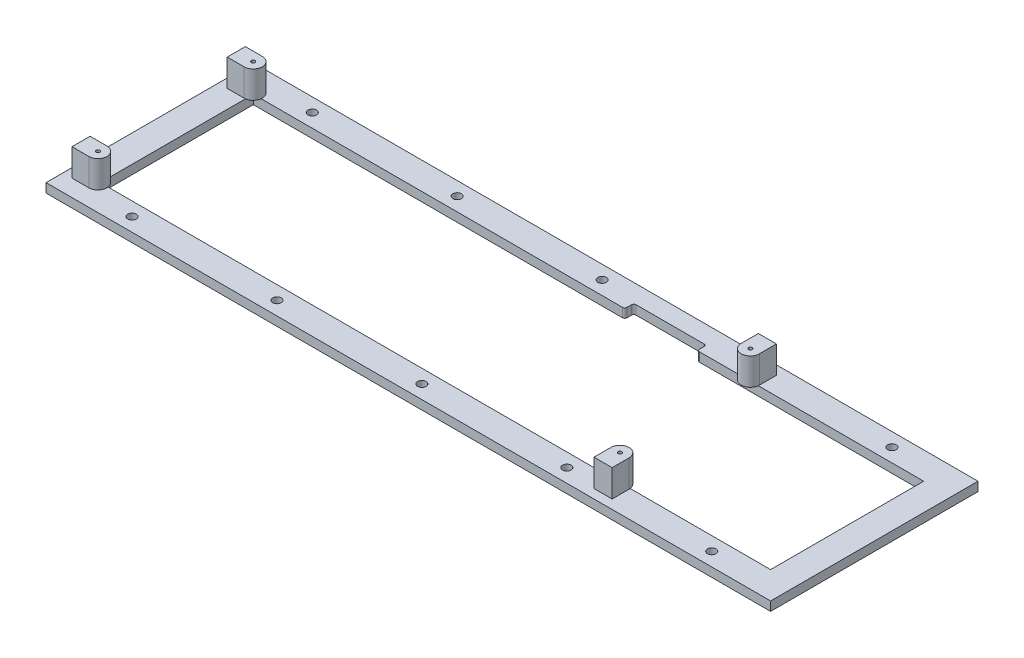
SolidWorks part; units mm, degrees
ref_plane "Front Plane" through (0, 0, 0) normal (0, 0, 1) x (1, 0, 0)
ref_plane "Top Plane" through (0, 0, 0) normal (0, 1, 0) x (1, 0, 0)
ref_plane "Right Plane" through (0, 0, 0) normal (1, 0, 0) x (0, 0, -1)
sketch "Sketch1" plane through (0, 0, 0) normal (0, 1, 0) x (1, 0, 0)
  line L0 (3.175, 3.175) -> (3.175, 69.5249) construction
  line L1 (0, 0) -> (254, 0)
  line L2 (0, 0) -> (0, 72.6999)
  line L3 (0, 72.6999) -> (254, 72.6999)
  line L4 (254, 0) -> (254, 72.6999)
  line L5 (6.35, 66.3499) -> (194.85, 66.3499) construction
  line L6 (6.35, 66.3499) -> (6.35, 6.35) construction
  line L7 (6.35, 6.35) -> (194.85, 6.35) construction
  line L8 (194.85, 66.3499) -> (194.85, 6.35) construction
  line L9 (3.175, 69.5249) -> (250.825, 69.5249) construction
  line L10 (250.825, 3.175) -> (250.825, 69.5249) construction
  line L11 (3.175, 3.175) -> (250.825, 3.175) construction
  line L12 (562.1369, 340.2788) -> (1927.4703, 340.2788) construction
  line L13 (3.175, 3.175) -> (3.175, 69.5249) construction
  line L28 (127, 72.6999) -> (127, 0) construction
  line L29 (127, 69.5249) -> (127, 66.3499) construction
  line L30 (0, 36.3499) -> (254, 36.3499) construction
  line L32 (6.35, 66.284) -> (6.35, 6.35) construction
  line L33 (6.35, 6.35) -> (194.851, 6.35) construction
  line L34 (194.851, 66.284) -> (194.851, 6.35) construction
  line L52 (-1511.8018, 332.3966) -> (-146.4685, 332.3966) construction
  line L54 (244.475, 63.1749) -> (244.475, 9.525)
  line L55 (244.475, 9.525) -> (9.525, 9.525)
  line L56 (9.525, 63.1749) -> (9.525, 9.525)
  line L57 (244.475, 63.1749) -> (9.525, 9.525) construction
  line L58 (244.475, 9.525) -> (9.525, 63.1749) construction
  line L62 (140.4938, 66.3499) -> (164.3062, 66.3499)
  line L63 (165.1, 63.9686) -> (165.1, 65.5561)
  line L64 (165.8938, 63.1749) -> (244.475, 63.1749)
  line L65 (127, 67.9374) -> (177.8, 67.9374) construction
  line L66 (139.7, 65.5561) -> (139.7, 63.9686)
  line L67 (138.9062, 63.1749) -> (9.525, 63.1749)
  line L68 (180.1749, 69.5249) -> (186.5249, 69.5249)
  line L69 (180.1749, 69.5249) -> (180.1749, 63.5332)
  line L70 (180.1749, 63.5332) -> (186.5249, 63.5332) construction
  line L71 (186.5249, 69.5249) -> (186.5249, 63.5332)
  line L72 (188.9252, 9.1008) -> (195.2752, 9.1008) construction
  line L73 (188.9252, 9.1008) -> (188.9252, 3.175)
  line L74 (188.9252, 3.175) -> (195.2752, 3.175)
  line L75 (195.2752, 9.1008) -> (195.2752, 3.175)
  line L76 (3.175, 12.2758) -> (9.1008, 12.2758)
  line L77 (3.175, 12.2758) -> (3.175, 5.9258)
  line L78 (3.175, 5.9258) -> (9.1008, 5.9258)
  line L79 (9.1008, 12.2758) -> (9.1008, 5.9258) construction
  line L80 (3.175, 66.7082) -> (9.1008, 66.7082)
  line L81 (3.175, 66.7082) -> (3.175, 60.3582)
  line L82 (3.175, 60.3582) -> (9.1008, 60.3582)
  line L83 (9.1008, 66.7082) -> (9.1008, 60.3582) construction
  circle A0 centre (177.8, 67.9374) radius 1.5
  circle A1 centre (177.8, 4.7625) radius 1.5
  circle A2 centre (228.6, 67.9374) radius 1.5
  circle A3 centre (228.6, 4.7625) radius 1.5
  circle A4 centre (214.0118, 59.3649) radius 3.81 construction
  circle A15 centre (127, 67.9374) radius 1.5
  circle A20 centre (127, 4.7625) radius 1.5
  circle A21 centre (25.4, 4.7625) radius 1.5
  circle A22 centre (76.2, 4.7625) radius 1.5
  circle A23 centre (25.4, 67.9374) radius 1.5
  circle A24 centre (76.2, 67.9374) radius 1.5
  circle A33 centre (9.1008, 63.5332) radius 0.635
  circle A34 centre (9.1008, 9.1008) radius 0.635
  circle A35 centre (192.1002, 9.1008) radius 0.635
  circle A36 centre (183.3499, 63.5332) radius 0.635
  arc A39 (139.7, 65.5561) -> (140.4938, 66.3499) centre (140.4938, 65.5561) cw
  arc A40 (164.3062, 66.3499) -> (165.1, 65.5561) centre (164.3062, 65.5561) cw
  arc A41 (165.8938, 63.1749) -> (165.1, 63.9686) centre (165.8938, 63.9686) cw
  arc A42 (139.7, 63.9686) -> (138.9062, 63.1749) centre (138.9062, 63.9686) cw
  arc A43 (180.1749, 63.5332) -> (186.5249, 63.5332) centre (183.3499, 63.5332) ccw
  arc A44 (195.2752, 9.1008) -> (188.9252, 9.1008) centre (192.1002, 9.1008) ccw
  arc A45 (9.1008, 12.2758) -> (9.1008, 5.9258) centre (9.1008, 9.1008) cw
  arc A46 (9.1008, 60.3582) -> (9.1008, 66.7082) centre (9.1008, 63.5332) ccw
  point P33 (127, 36.3499)
  point P48 (127, 67.9374)
  point P72 (0, 0)
  point P73 (0, 0)
  point P74 (0, 0)
  point P75 (0, 0)
  point P78 (0, 0)
  point P79 (0, 0)
  point P91 (152.4, 67.9374)
  point P93 (152.4, 66.3499)
  point P96 (165.1, 66.3499)
  dimension "D6" = 3.175
  dimension "D11" = 7.62
  dimension "D13" = 188.5
  dimension "D15" = 3
  dimension "D21" = 2.8167
  dimension "D19" = 1.27
  dimension "D24" = 185.7502
  dimension "D18" = 2.7508
  dimension "D20" = 2.7508
  dimension "D33" = 0.7937
  dimension "D23" = 6.35
  dimension "D22" = 176.9999
  dimension "D1" = 59.9999
  dimension "D2" = 3.175
  dimension "D3" = 3.175
  dimension "D4" = 3.175
  dimension "D5" = 3.175
  dimension "D7" = 3.175
  dimension "D8" = 3.175
  dimension "D9" = 19.1618
  dimension "D10" = 10.16
  dimension "D12" = 72.6999
  dimension "D14" = 254
  dimension "D16" = 3
  dimension "D17" = 50.8
  dimension "D25" = 6.35
  dimension "D26" = 3.175
  dimension "D27" = 9.525
  dimension "D28" = 25.4
  dimension "D29" = 9.525
  dimension "D30" = 9.525
  dimension "D31" = 9.525
  dimension "D32" = 9.525
  dimension "D34" = 6.35
  dimension "D35" = 6.35
  dimension "D36" = 3.8902
extrude "Boss-Extrude1" add sketch "Sketch1" against normal blind 3.175 contours L4 | L2 | L3 L4 L1 L2 | L67 L56 L55 L54 L64 A41 L63 A40 L62 A39 L66 A42 | A23 | A24 | A15 | A0 | A2 | A3 | A1 | A20 | A22 | A21 region at (2.642, 0, -36.3499)
extrude "Boss-Extrude2" add sketch "Sketch1<7>" along normal blind 9.525 contours L71 A43 L69 L68 | A44 L73 L74 L75 | A45 L78 L77 L76 | A34 | A35 | A36 | A33 | A46 L80 L81 L82
sketch "Sketch1<7>" plane through (0, 0, 0) normal (0, 1, 0) x (1, 0, 0) same geometry as "Sketch1"
